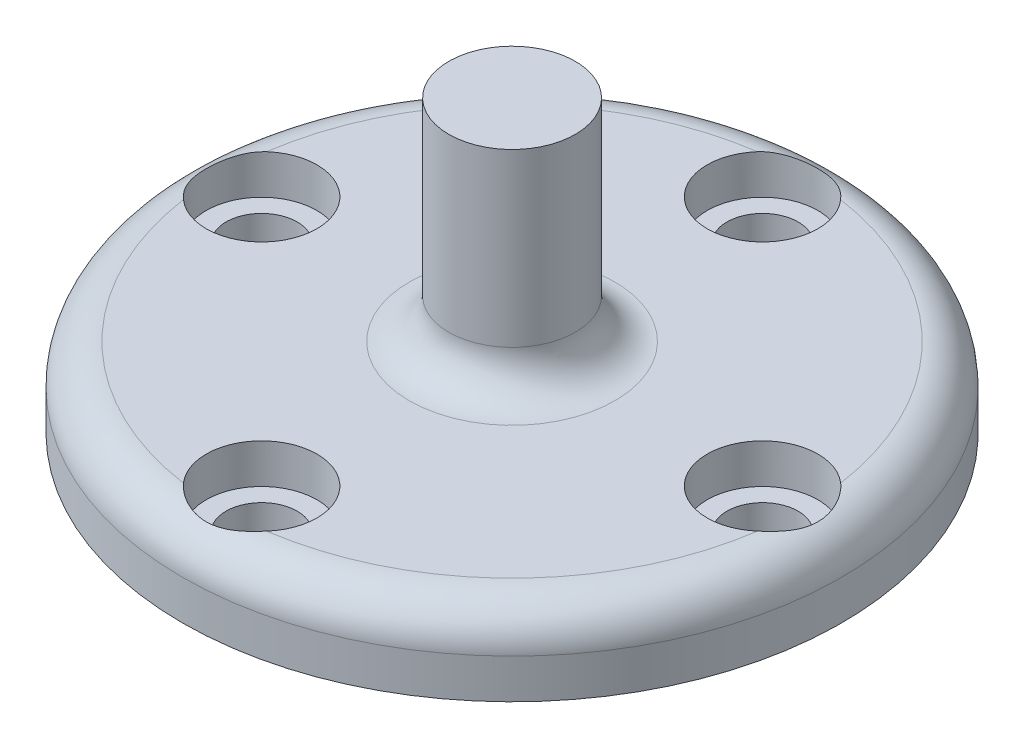
SolidWorks part; units mm, degrees
ref_plane "Front Plane" through (0, 0, 0) normal (0, 0, 1) x (1, 0, 0)
ref_plane "Top Plane" through (0, 0, 0) normal (0, 1, 0) x (1, 0, 0)
ref_plane "Right Plane" through (0, 0, 0) normal (1, 0, 0) x (0, 0, -1)
sketch "Sketch1" plane through (0, 0, 0) normal (0, 1, 0) x (1, 0, 0)
  circle A0 centre (0, 0) radius 12.5
  dimension "D1" = 25
extrude "Boss-Extrude1" add sketch "Sketch1" along normal blind 3
sketch "Sketch2" plane through (0, 3, 0) normal (0, 1, 0) x (1, 0, 0)
  circle A0 centre (0, 0) radius 9.5 construction
  circle A1 centre (0, 9.5) radius 1.35
  dimension "D1" = 19
  dimension "D2" = 2.7
extrude "Cut-Extrude1" cut sketch "Sketch2" against normal through all
sketch "Sketch4" plane through (0, 3, 0) normal (0, 1, 0) x (1, 0, 0)
  circle A0 centre (0, 9.5) radius 2.1
  dimension "D1" = 4.2
extrude "Cut-Extrude2" cut sketch "Sketch4" against normal blind 1.5
pattern_circular "CirPattern1" count 4 over 360 about axis through (0, 3, 0) along (0, -1, 0) of "Cut-Extrude1", "Cut-Extrude2"
sketch "Sketch3" plane through (0, 3, 0) normal (0, 1, 0) x (1, 0, 0)
  circle A0 centre (0, 0) radius 2.4
  dimension "D1" = 4.8
extrude "Boss-Extrude2" add sketch "Sketch3" along normal blind 8
fillet "Fillet1" radius 1.5 2 edges at (0, 3, 12.5) (0, 3, 2.4)
